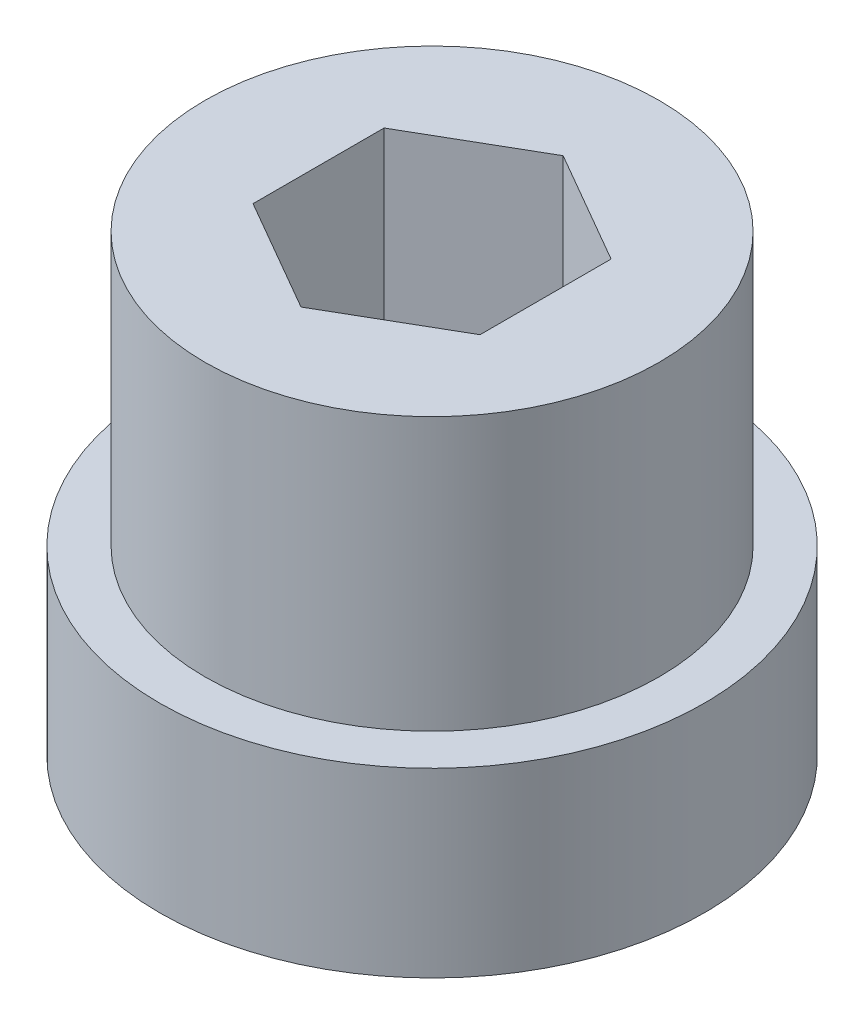
SolidWorks part; units mm, degrees
ref_plane "Front Plane" through (0, 0, 0) normal (0, 0, 1) x (1, 0, 0)
ref_plane "Top Plane" through (0, 0, 0) normal (0, 1, 0) x (1, 0, 0)
ref_plane "Right Plane" through (0, 0, 0) normal (1, 0, 0) x (0, 0, -1)
sketch "Sketch1" plane through (0, 0, 0) normal (0, 1, 0) x (1, 0, 0)
  circle A0 centre (0, 0) radius 7
  dimension "D1" = 14
extrude "Boss-Extrude1" add sketch "Sketch1" along normal blind 4
sketch "Sketch2" plane through (0, 4, 0) normal (0, 1, 0) x (1, 0, 0)
  circle A0 centre (0, 0) radius 5
  dimension "D1" = 10
extrude "Boss-Extrude2" add sketch "Sketch2" along normal blind 6
sketch "Sketch3" plane through (0, 10, 0) normal (0, 1, 0) x (1, 0, 0)
  line L1 (3.5, -1.4434) -> (3.5, 1.4434)
  line L2 (3.5, 1.4434) -> (1, 2.8868)
  line L3 (1, 2.8868) -> (-1.5, 1.4434)
  line L4 (-1.5, 1.4434) -> (-1.5, -1.4434)
  line L5 (-1.5, -1.4434) -> (1, -2.8868)
  line L6 (1, -2.8868) -> (3.5, -1.4434)
  circle A0 centre (1, 0) radius 2.5 construction
  dimension "D1" = 5
  dimension "D2" = 1
extrude "Cut-Extrude1" [suppressed] cut sketch "Sketch3" against normal through all
sketch "Sketch4" plane through (0, 10, 0) normal (0, 1, 0) x (1, 0, 0)
  line L1 (2.5, 1.4434) -> (0, 2.8868)
  line L2 (0, 2.8868) -> (-2.5, 1.4434)
  line L3 (-2.5, 1.4434) -> (-2.5, -1.4434)
  line L4 (-2.5, -1.4434) -> (0, -2.8868)
  line L5 (0, -2.8868) -> (2.5, -1.4434)
  line L6 (2.5, -1.4434) -> (2.5, 1.4434)
  circle A0 centre (0, 0) radius 2.5 construction
  dimension "D1" = 5
extrude "Cut-Extrude2" cut sketch "Sketch4" against normal through all
sketch "Sketch5" plane through (0, 4, 0) normal (0, 1, 0) x (1, 0, 0)
  circle A0 centre (0, 0) radius 6
  dimension "D1" = 12
extrude "Cut-Extrude3" cut sketch "Sketch5" against normal through all flip side to cut
equation "\"R_ROLL\"= 5mm"
equation "\"D_SUN\"= 80mm"
equation "\"NUM_ROLL\"= 16"
equation "\"RHO\"= 1mm"
equation "\"D_SHAFT\"= 15mm"
equation "\"D_OUTPUT\"= 40mm"
equation "\"NUM_OUT\"= 6"
equation "\"R_OUT_ROLL\"= 5mm"
